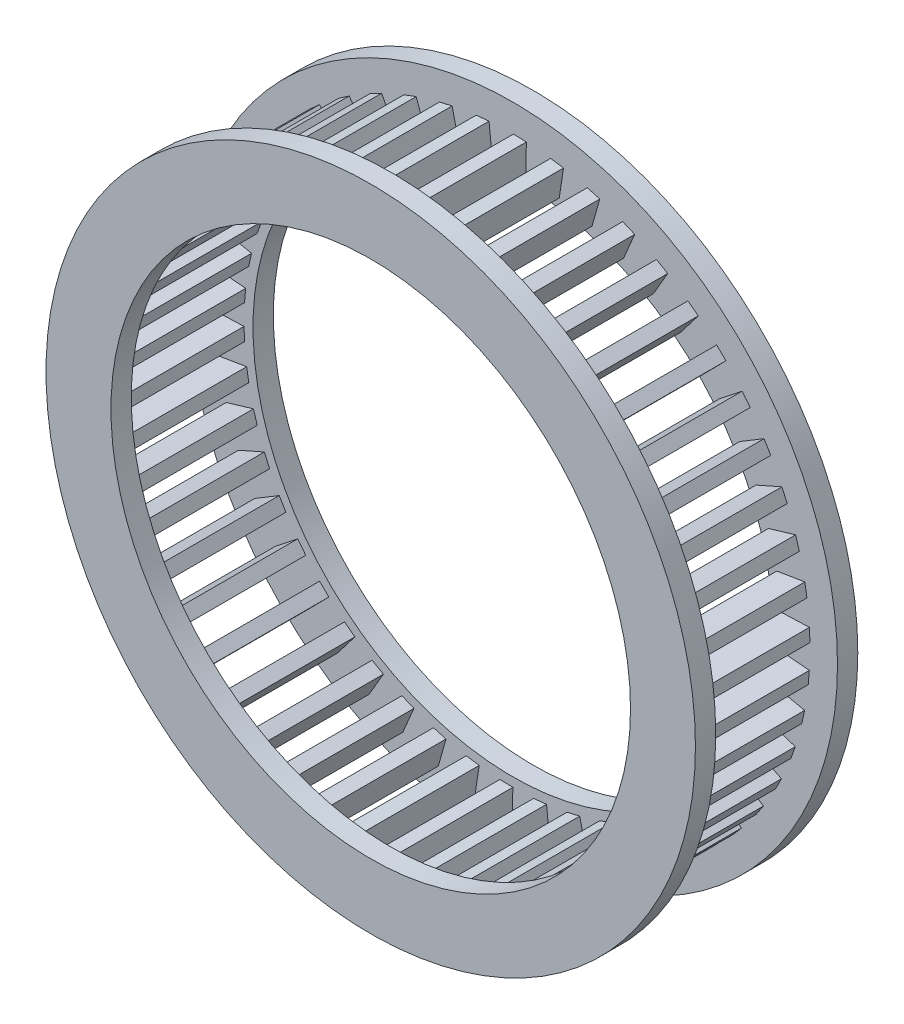
SolidWorks part; units mm, degrees
ref_plane "Спереди" through (0, 0, 0) normal (0, 0, 1) x (1, 0, 0)
ref_plane "Сверху" through (0, 0, 0) normal (0, 1, 0) x (1, 0, 0)
ref_plane "Справа" through (0, 0, 0) normal (1, 0, 0) x (0, 0, -1)
sketch "Эскиз1" plane through (0, 0, 0) normal (0, 0, 1) x (1, 0, 0)
  line L0 (66.2121, 0.9794) -> (73.2068, 1.2521)
  line L1 (73.2068, 1.2521) -> (73.0822, 4.4496)
  line L2 (73.0822, 4.4496) -> (66.0875, 4.177)
  line L3 (66.0875, 4.177) -> (66.2121, 0.9794)
  line L4 (65.5672, 9.2703) -> (72.4726, 10.4174)
  line L5 (72.4726, 10.4174) -> (71.9482, 13.5742)
  line L6 (71.9482, 13.5742) -> (65.0428, 12.427)
  line L7 (65.0428, 12.427) -> (65.5672, 9.2703)
  line L8 (63.8883, 17.4149) -> (70.5955, 19.4185)
  line L9 (70.5955, 19.4185) -> (69.6796, 22.4846)
  line L10 (69.6796, 22.4846) -> (62.9724, 20.4811)
  line L11 (62.9724, 20.4811) -> (63.8883, 17.4149)
  line L12 (61.2019, 25.2849) -> (67.605, 28.1133)
  line L13 (67.605, 28.1133) -> (66.312, 31.0405)
  line L14 (66.312, 31.0405) -> (59.9089, 28.2121)
  line L15 (59.9089, 28.2121) -> (61.2019, 25.2849)
  line L16 (57.5503, 32.7562) -> (63.5484, 36.3648)
  line L17 (63.5484, 36.3648) -> (61.8988, 39.1068)
  line L18 (61.8988, 39.1068) -> (55.9006, 35.4982)
  line L19 (55.9006, 35.4982) -> (57.5503, 32.7562)
  line L20 (52.991, 39.7109) -> (58.4896, 44.0428)
  line L21 (58.4896, 44.0428) -> (56.5093, 46.5564)
  line L22 (56.5093, 46.5564) -> (51.0107, 42.2245)
  line L23 (51.0107, 42.2245) -> (52.991, 39.7109)
  line L24 (47.5961, 46.0393) -> (52.5084, 51.0262)
  line L25 (52.5084, 51.0262) -> (50.2286, 53.2718)
  line L26 (50.2286, 53.2718) -> (45.3163, 48.2849)
  line L27 (45.3163, 48.2849) -> (47.5961, 46.0393)
  line L28 (41.4505, 51.6416) -> (45.699, 57.2049)
  line L29 (45.699, 57.2049) -> (43.1558, 59.1471)
  line L30 (43.1558, 59.1471) -> (38.9073, 53.5838)
  line L31 (38.9073, 53.5838) -> (41.4505, 51.6416)
  line L32 (34.6512, 56.4295) -> (38.169, 62.4814)
  line L33 (38.169, 62.4814) -> (35.4024, 64.0895)
  line L34 (35.4024, 64.0895) -> (31.8847, 58.0376)
  line L35 (31.8847, 58.0376) -> (34.6512, 56.4295)
  line L36 (27.3055, 60.3275) -> (30.037, 66.7726)
  line L37 (30.037, 66.7726) -> (27.0907, 68.0213)
  line L38 (27.0907, 68.0213) -> (24.3592, 61.5762)
  line L39 (24.3592, 61.5762) -> (27.3055, 60.3275)
  line L40 (19.5292, 63.2741) -> (21.4314, 70.0107)
  line L41 (21.4314, 70.0107) -> (18.3518, 70.8803)
  line L42 (18.3518, 70.8803) -> (16.4496, 64.1437)
  line L43 (16.4496, 64.1437) -> (19.5292, 63.2741)
  line L44 (11.4448, 65.2228) -> (12.4877, 72.1447)
  line L45 (12.4877, 72.1447) -> (9.3234, 72.6214)
  line L46 (9.3234, 72.6214) -> (8.2805, 65.6996)
  line L47 (8.2805, 65.6996) -> (11.4448, 65.2228)
  line L48 (3.18, 66.1429) -> (3.3471, 73.1409)
  line L49 (3.3471, 73.1409) -> (0.148, 73.2173)
  line L50 (0.148, 73.2173) -> (-0.0191, 66.2193)
  line L51 (-0.0191, 66.2193) -> (3.18, 66.1429)
  line L52 (-5.135, 66.0199) -> (-5.8463, 72.9837)
  line L53 (-5.8463, 72.9837) -> (-9.0297, 72.6585)
  line L54 (-9.0297, 72.6585) -> (-8.3184, 65.6948)
  line L55 (-8.3184, 65.6948) -> (-5.135, 66.0199)
  line L56 (-13.369, 64.8558) -> (-14.9475, 71.6755)
  line L57 (-14.9475, 71.6755) -> (-18.065, 70.9539)
  line L58 (-18.065, 70.9539) -> (-16.4866, 64.1342)
  line L59 (-16.4866, 64.1342) -> (-13.369, 64.8558)
  line L60 (-21.3922, 62.6688) -> (-23.8129, 69.2369)
  line L61 (-23.8129, 69.2369) -> (-26.8155, 68.1302)
  line L62 (-26.8155, 68.1302) -> (-24.3947, 61.5621)
  line L63 (-24.3947, 61.5621) -> (-21.3922, 62.6688)
  line L64 (-29.078, 59.4935) -> (-32.3028, 65.7064)
  line L65 (-32.3028, 65.7064) -> (-35.143, 64.2321)
  line L66 (-35.143, 64.2321) -> (-31.9181, 58.0192)
  line L67 (-31.9181, 58.0192) -> (-29.078, 59.4935)
  line L68 (-36.3052, 55.3799) -> (-40.2833, 61.1396)
  line L69 (-40.2833, 61.1396) -> (-42.9163, 59.3211)
  line L70 (-42.9163, 59.3211) -> (-38.9382, 53.5613)
  line L71 (-38.9382, 53.5613) -> (-36.3052, 55.3799)
  line L72 (-42.9598, 50.393) -> (-47.6285, 55.6087)
  line L73 (-47.6285, 55.6087) -> (-50.0128, 53.4745)
  line L74 (-50.0128, 53.4745) -> (-45.3442, 48.2587)
  line L75 (-45.3442, 48.2587) -> (-42.9598, 50.393)
  line L76 (-48.937, 44.6113) -> (-54.2225, 49.2008)
  line L77 (-54.2225, 49.2008) -> (-56.3206, 46.7845)
  line L78 (-56.3206, 46.7845) -> (-51.035, 42.1951)
  line L79 (-51.035, 42.1951) -> (-48.937, 44.6113)
  line L80 (-54.1424, 38.1261) -> (-59.9615, 42.0169)
  line L81 (-59.9615, 42.0169) -> (-61.7401, 39.3568)
  line L82 (-61.7401, 39.3568) -> (-55.9211, 35.466)
  line L83 (-55.9211, 35.466) -> (-54.1424, 38.1261)
  line L84 (-58.4939, 31.0396) -> (-64.7548, 34.1705)
  line L85 (-64.7548, 34.1705) -> (-66.186, 31.3084)
  line L86 (-66.186, 31.3084) -> (-59.9252, 28.1775)
  line L87 (-59.9252, 28.1775) -> (-58.4939, 31.0396)
  line L88 (-61.923, 23.4636) -> (-68.5269, 25.7851)
  line L89 (-68.5269, 25.7851) -> (-69.5881, 22.7662)
  line L90 (-69.5881, 22.7662) -> (-62.9842, 20.4447)
  line L91 (-62.9842, 20.4447) -> (-61.923, 23.4636)
  line L92 (-64.3755, 15.5176) -> (-71.2182, 16.9931)
  line L93 (-71.2182, 16.9931) -> (-71.8927, 13.865)
  line L94 (-71.8927, 13.865) -> (-65.05, 12.3895)
  line L95 (-65.05, 12.3895) -> (-64.3755, 15.5176)
  line L96 (-65.8127, 7.3269) -> (-72.7864, 7.9331)
  line L97 (-72.7864, 7.9331) -> (-73.0636, 4.7451)
  line L98 (-73.0636, 4.7451) -> (-66.0899, 4.1389)
  line L99 (-66.0899, 4.1389) -> (-65.8127, 7.3269)
  line L100 (-66.2121, -0.9794) -> (-73.2068, -1.2521)
  line L101 (-73.2068, -1.2521) -> (-73.0822, -4.4496)
  line L102 (-73.0822, -4.4496) -> (-66.0875, -4.177)
  line L103 (-66.0875, -4.177) -> (-66.2121, -0.9794)
  line L104 (-65.5672, -9.2703) -> (-72.4726, -10.4174)
  line L105 (-72.4726, -10.4174) -> (-71.9482, -13.5742)
  line L106 (-71.9482, -13.5742) -> (-65.0428, -12.427)
  line L107 (-65.0428, -12.427) -> (-65.5672, -9.2703)
  line L108 (-63.8883, -17.4149) -> (-70.5955, -19.4185)
  line L109 (-70.5955, -19.4185) -> (-69.6796, -22.4846)
  line L110 (-69.6796, -22.4846) -> (-62.9724, -20.4811)
  line L111 (-62.9724, -20.4811) -> (-63.8883, -17.4149)
  line L112 (-61.2019, -25.2849) -> (-67.605, -28.1133)
  line L113 (-67.605, -28.1133) -> (-66.312, -31.0405)
  line L114 (-66.312, -31.0405) -> (-59.9089, -28.2121)
  line L115 (-59.9089, -28.2121) -> (-61.2019, -25.2849)
  line L116 (-57.5503, -32.7562) -> (-63.5484, -36.3648)
  line L117 (-63.5484, -36.3648) -> (-61.8988, -39.1068)
  line L118 (-61.8988, -39.1068) -> (-55.9006, -35.4982)
  line L119 (-55.9006, -35.4982) -> (-57.5503, -32.7562)
  line L120 (-52.991, -39.7109) -> (-58.4896, -44.0428)
  line L121 (-58.4896, -44.0428) -> (-56.5093, -46.5564)
  line L122 (-56.5093, -46.5564) -> (-51.0107, -42.2245)
  line L123 (-51.0107, -42.2245) -> (-52.991, -39.7109)
  line L124 (-47.5961, -46.0393) -> (-52.5084, -51.0262)
  line L125 (-52.5084, -51.0262) -> (-50.2286, -53.2718)
  line L126 (-50.2286, -53.2718) -> (-45.3163, -48.2849)
  line L127 (-45.3163, -48.2849) -> (-47.5961, -46.0393)
  line L128 (-41.4505, -51.6416) -> (-45.699, -57.2049)
  line L129 (-45.699, -57.2049) -> (-43.1558, -59.1471)
  line L130 (-43.1558, -59.1471) -> (-38.9073, -53.5838)
  line L131 (-38.9073, -53.5838) -> (-41.4505, -51.6416)
  line L132 (-34.6512, -56.4295) -> (-38.169, -62.4814)
  line L133 (-38.169, -62.4814) -> (-35.4024, -64.0895)
  line L134 (-35.4024, -64.0895) -> (-31.8847, -58.0376)
  line L135 (-31.8847, -58.0376) -> (-34.6512, -56.4295)
  line L136 (-27.3055, -60.3275) -> (-30.037, -66.7726)
  line L137 (-30.037, -66.7726) -> (-27.0907, -68.0213)
  line L138 (-27.0907, -68.0213) -> (-24.3592, -61.5762)
  line L139 (-24.3592, -61.5762) -> (-27.3055, -60.3275)
  line L140 (-19.5292, -63.2741) -> (-21.4314, -70.0107)
  line L141 (-21.4314, -70.0107) -> (-18.3518, -70.8803)
  line L142 (-18.3518, -70.8803) -> (-16.4496, -64.1437)
  line L143 (-16.4496, -64.1437) -> (-19.5292, -63.2741)
  line L144 (-11.4448, -65.2228) -> (-12.4877, -72.1447)
  line L145 (-12.4877, -72.1447) -> (-9.3234, -72.6214)
  line L146 (-9.3234, -72.6214) -> (-8.2805, -65.6996)
  line L147 (-8.2805, -65.6996) -> (-11.4448, -65.2228)
  line L148 (-3.18, -66.1429) -> (-3.3471, -73.1409)
  line L149 (-3.3471, -73.1409) -> (-0.148, -73.2173)
  line L150 (-0.148, -73.2173) -> (0.0191, -66.2193)
  line L151 (0.0191, -66.2193) -> (-3.18, -66.1429)
  line L152 (5.135, -66.0199) -> (5.8463, -72.9837)
  line L153 (5.8463, -72.9837) -> (9.0297, -72.6585)
  line L154 (9.0297, -72.6585) -> (8.3184, -65.6948)
  line L155 (8.3184, -65.6948) -> (5.135, -66.0199)
  line L156 (13.369, -64.8558) -> (14.9475, -71.6755)
  line L157 (14.9475, -71.6755) -> (18.065, -70.9539)
  line L158 (18.065, -70.9539) -> (16.4866, -64.1342)
  line L159 (16.4866, -64.1342) -> (13.369, -64.8558)
  line L160 (21.3922, -62.6688) -> (23.8129, -69.2369)
  line L161 (23.8129, -69.2369) -> (26.8155, -68.1302)
  line L162 (26.8155, -68.1302) -> (24.3947, -61.5621)
  line L163 (24.3947, -61.5621) -> (21.3922, -62.6688)
  line L164 (29.078, -59.4935) -> (32.3028, -65.7064)
  line L165 (32.3028, -65.7064) -> (35.143, -64.2321)
  line L166 (35.143, -64.2321) -> (31.9181, -58.0192)
  line L167 (31.9181, -58.0192) -> (29.078, -59.4935)
  line L168 (36.3052, -55.3799) -> (40.2833, -61.1396)
  line L169 (40.2833, -61.1396) -> (42.9163, -59.3211)
  line L170 (42.9163, -59.3211) -> (38.9382, -53.5613)
  line L171 (38.9382, -53.5613) -> (36.3052, -55.3799)
  line L172 (42.9598, -50.393) -> (47.6285, -55.6087)
  line L173 (47.6285, -55.6087) -> (50.0128, -53.4745)
  line L174 (50.0128, -53.4745) -> (45.3442, -48.2587)
  line L175 (45.3442, -48.2587) -> (42.9598, -50.393)
  line L176 (48.937, -44.6113) -> (54.2225, -49.2008)
  line L177 (54.2225, -49.2008) -> (56.3206, -46.7845)
  line L178 (56.3206, -46.7845) -> (51.035, -42.1951)
  line L179 (51.035, -42.1951) -> (48.937, -44.6113)
  line L180 (54.1424, -38.1261) -> (59.9615, -42.0169)
  line L181 (59.9615, -42.0169) -> (61.7401, -39.3568)
  line L182 (61.7401, -39.3568) -> (55.9211, -35.466)
  line L183 (55.9211, -35.466) -> (54.1424, -38.1261)
  line L184 (58.4939, -31.0396) -> (64.7548, -34.1705)
  line L185 (64.7548, -34.1705) -> (66.186, -31.3084)
  line L186 (66.186, -31.3084) -> (59.9252, -28.1775)
  line L187 (59.9252, -28.1775) -> (58.4939, -31.0396)
  line L188 (61.923, -23.4636) -> (68.5269, -25.7851)
  line L189 (68.5269, -25.7851) -> (69.5881, -22.7662)
  line L190 (69.5881, -22.7662) -> (62.9842, -20.4447)
  line L191 (62.9842, -20.4447) -> (61.923, -23.4636)
  line L192 (64.3755, -15.5176) -> (71.2182, -16.9931)
  line L193 (71.2182, -16.9931) -> (71.8927, -13.865)
  line L194 (71.8927, -13.865) -> (65.05, -12.3895)
  line L195 (65.05, -12.3895) -> (64.3755, -15.5176)
  line L196 (65.8127, -7.3269) -> (72.7864, -7.9331)
  line L197 (72.7864, -7.9331) -> (73.0636, -4.7451)
  line L198 (73.0636, -4.7451) -> (66.0899, -4.1389)
  line L199 (66.0899, -4.1389) -> (65.8127, -7.3269)
extrude "Cage_50_bars" add sketch "Эскиз1" along normal blind 30.2 from offset 15.1 separate body offset against normal yes
sketch "Эскиз2" plane through (0, 0, 0) normal (0, 0, 1) x (1, 0, 0)
  circle A0 centre (0, 0) radius 80
  circle A1 centre (0, 0) radius 64
extrude "Cage_ring_right" add sketch "Эскиз2" along normal blind 5 from offset 15
sketch "Эскиз3" plane through (0, 0, 0) normal (0, 0, 1) x (1, 0, 0)
  circle A0 centre (0, 0) radius 80
  circle A1 centre (0, 0) radius 64
extrude "Cage_ring_left" add sketch "Эскиз3" along normal blind 5 from offset 20 offset against normal yes
